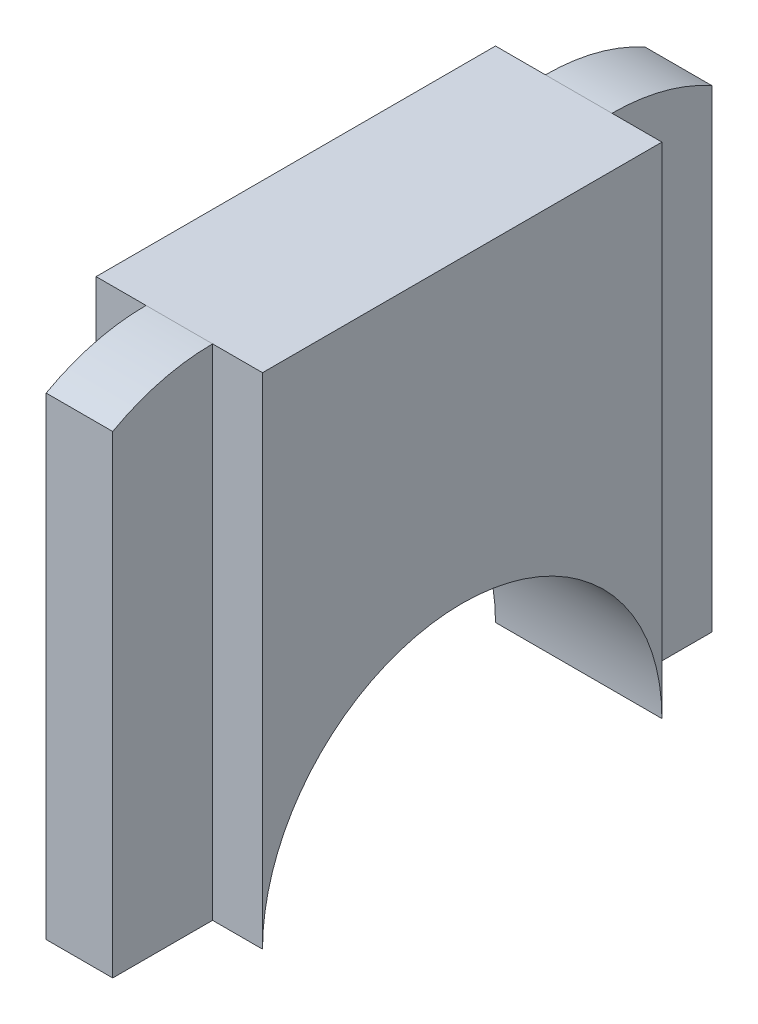
SolidWorks part; units mm, degrees
ref_plane "Front Plane" through (0, 0, 0) normal (0, 0, 1) x (1, 0, 0)
ref_plane "Top Plane" through (0, 0, 0) normal (0, 1, 0) x (1, 0, 0)
ref_plane "Right Plane" through (0, 0, 0) normal (1, 0, 0) x (0, 0, -1)
sketch "Sketch1" plane through (0, 0, 0) normal (1, 0, 0) x (0, 0, -1)
  line L0 (0, 0) -> (0, 15.8754) construction
  line L1 (-6, 15) -> (6, 15)
  line L2 (-6, 15) -> (-6, 0)
  line L3 (-6, 0) -> (6, 0)
  line L4 (6, 15) -> (6, 0)
  line L6 (-6, 15) -> (-6, 0)
  line L7 (-6, 0) -> (-9, 0)
  line L10 (9, 14.22) -> (9, 0)
  line L11 (6, 0) -> (9, 0)
  line L12 (-9, 14.22) -> (-9, 0)
  arc A0 (-6, 0) -> (6, 0) centre (0, 0) cw
  arc A1 (-6, 15) -> (-9, 14.22) centre (-6, 8.8408) ccw
  arc A2 (6, 15) -> (9, 14.22) centre (6, 8.8408) cw
  point P4 (0, 0)
  point P16 (-6, 5)
  point P18 (0, 0)
  dimension "D1" = 15
  dimension "D2" = 12
  dimension "D3" = 3
  dimension "D4" = 0.78
extrude "Boss-Extrude1" add sketch "Sketch1" along normal blind 2.5 and the other way blind 2.5 contours A0 L0 L1 L2 | L0 A0 L4 L1 region at (0, 9.769, 3.2077) region at (0, 9.769, -3.2077)
extrude "Boss-Extrude2" add sketch "Sketch1<3>" along normal blind 1 and the other way blind 1
sketch "Sketch1<3>" plane through (0, 0, 0) normal (1, 0, 0) x (0, 0, -1) same geometry as "Sketch1"
